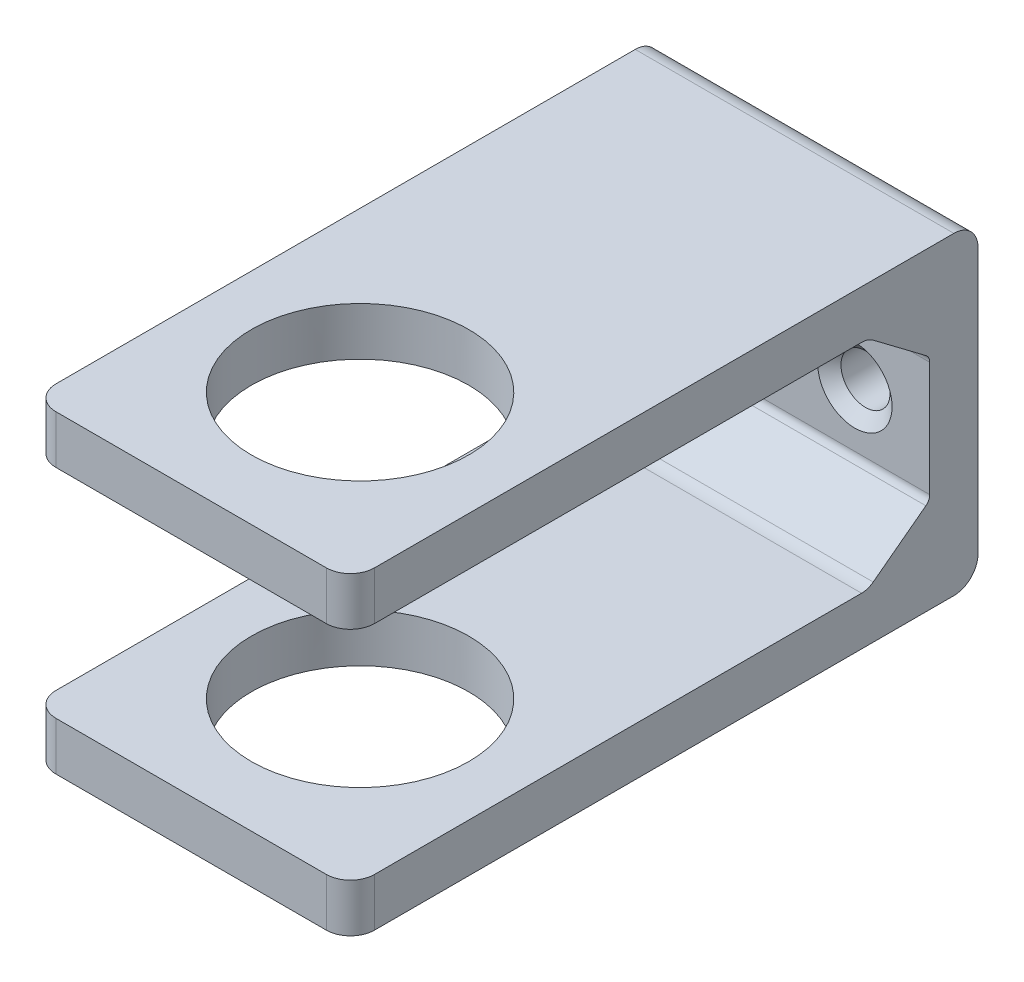
SolidWorks part; units mm, degrees
ref_plane "Front Plane" through (0, 0, 0) normal (0, 0, 1) x (1, 0, 0)
ref_plane "Top Plane" through (0, 0, 0) normal (0, 1, 0) x (1, 0, 0)
ref_plane "Right Plane" through (0, 0, 0) normal (1, 0, 0) x (0, 0, -1)
sketch "Sketch1" plane through (0, 0, 0) normal (0, 1, 0) x (1, 0, 0)
  line L1 (-20.955, -41.275) -> (20.955, -41.275)
  line L2 (-20.955, -41.275) -> (-20.955, 41.275)
  line L3 (-20.955, 41.275) -> (20.955, 41.275)
  line L4 (20.955, -41.275) -> (20.955, 41.275)
  line L5 (-20.955, -41.275) -> (20.955, 41.275) construction
  line L6 (-20.955, 41.275) -> (20.955, -41.275) construction
  point P0 (0, 0)
  dimension "D1" = 41.91
  dimension "D2" = 82.55
extrude "Boss-Extrude1" add sketch "Sketch1" along normal blind 41.275
sketch "Sketch13" plane through (-20.955, 0, 0) normal (-1, 0, 0) x (0, 0, 1)
  line L0 (-34.925, 28.8106) -> (-26.8109, 34.925)
  line L1 (-26.8109, 34.925) -> (41.275, 34.925)
  line L2 (-34.925, 28.8106) -> (-34.925, 12.4644)
  line L3 (-26.8109, 6.35) -> (41.275, 6.35)
  line L4 (-41.275, 0) -> (41.275, 0)
  line L5 (41.275, 0) -> (41.275, 41.275)
  line L6 (41.275, 41.275) -> (-41.275, 41.275)
  line L7 (-41.275, 41.275) -> (-41.275, 0)
  line L8 (-41.275, 0) -> (41.275, 0)
  line L9 (41.275, 0) -> (41.275, 41.275)
  line L10 (41.275, 41.275) -> (-41.275, 41.275)
  line L11 (-41.275, 41.275) -> (-41.275, 0)
  line L12 (41.275, 34.925) -> (41.275, 6.35)
  line L13 (-34.925, 12.4644) -> (-26.8109, 6.35)
  line M11 (41.275, 0) -> (41.275, 41.275)
  dimension "D2" = 6.35
  dimension "D3" = 6.35
  dimension "D4" = 6.35
  dimension "D5" = 10.16
  dimension "D6" = 143
  dimension "D7" = 143
  dimension "D8" = 68.0859
  dimension "D1" = 0
extrude "Cut-Extrude6" cut sketch "Sketch13" against normal through all contours L2 L13 L3 L1 L0 M11 region at (-20.955, 20.6375, 4.0003)
sketch "Sketch3" plane through (0, 41.275, 0) normal (0, 1, 0) x (1, 0, 0)
  line L1 (20.955, 41.275) -> (-20.955, 41.275) construction
  line L3 (2.7496, -14.2875) -> (-2.7496, -14.2875)
  line L4 (-2.7496, -14.2875) -> (-5.4993, -19.05)
  line L5 (-5.4993, -19.05) -> (-2.7496, -23.8125)
  line L6 (-2.7496, -23.8125) -> (2.7496, -23.8125)
  line L7 (2.7496, -23.8125) -> (5.4993, -19.05)
  line L8 (5.4993, -19.05) -> (2.7496, -14.2875)
  circle A0 centre (0, -19.05) radius 50.8
  circle A1 centre (0, -19.05) radius 4.7625 construction
  circle A2 centre (0, -19.05) radius 14.3002
  dimension "D1" = 101.6
  dimension "D2" = 9.525
  dimension "D3" = 9.525
  dimension "D4" = 28.6004
extrude "Cut-Extrude2" cut sketch "Sketch3" against normal through all contours L7 L8 L3 L4 L5 L6 | A2 L8 L7 L6 L5 L4 L3 region at (0, 41.275, 19.05) region at (-13.8957, 41.275, 19.05)
sketch "Sketch4" plane through (0, 0, -41.275) normal (0, 0, -1) x (-1, 0, 0)
  line L0 (-20.955, 20.6375) -> (20.955, 20.6375) construction
  line L1 (-20.955, 41.275) -> (-20.955, 0) construction
  line L2 (20.955, 41.275) -> (20.955, 0) construction
  line L3 (11.1125, 20.6375) -> (-11.1125, 20.6375) construction
  circle A0 centre (11.1125, 20.6375) radius 3.2258
  circle A1 centre (-11.1125, 20.6375) radius 3.2258
  point P10 (0, 20.6375)
  point P12 (0, 20.6375)
  dimension "D1" = 6.4516
  dimension "D2" = 22.225
extrude "Cut-Extrude3" cut sketch "Sketch4" against normal through all
fillet "Fillet2" radius 3.175 6 edges at (0, 0, -41.275) (0, 41.275, -41.275) (-20.955, 3.175, 41.275) (20.955, 3.175, 41.275) (-20.955, 38.1, 41.275) (20.955, 38.1, 41.275)
hole_wizard "CSK for #10 Flat Head Machine Screw (100)4" positions "Sketch14" profile "Sketch15" countersink size "#10" standard "ANSI Inch"
sketch "Sketch14" plane through (0, 0, -34.925) normal (0, 0, 1) x (1, 0, 0)
  point P0 (-11.1125, 20.6375)
  point P3 (11.1125, 20.6375)
sketch "Sketch15" plane through (-11.1125, 20.6375, -34.925) normal (1, 0, 0) x (0, -1, 0)
  line L0 (0, 0) -> (0, 8.0364)
  line L1 (0, 8.0364) -> (2.8067, 6.35)
  line L2 (2.8067, 6.35) -> (2.8067, 1.7477)
  line L3 (2.8067, 1.7477) -> (4.8895, 0)
  line L5 (4.8895, 0) -> (0, 0)
  line L6 (-2.8067, 1.7477) -> (-4.8895, 0) construction
  line L10 (0, 8.0364) -> (-2.8067, 6.35) construction
  line L11 (0, -6.35) -> (0, 107.95) construction
  dimension "Hole Dia." = 5.6134
  dimension "Hole Depth" = 6.35
  dimension "Near C'Sink Dia." = 9.779
  dimension "Near C'Sink Angle" = 100
  dimension "Drill Angle" = 118
fillet "Fillet3" radius 2.54 2 edges at (0, 6.35, -26.8109) (0, 34.925, -26.8109)
fillet "Fillet4" radius 1.27 2 edges at (0, 12.4644, -34.925) (0, 28.8106, -34.925)
